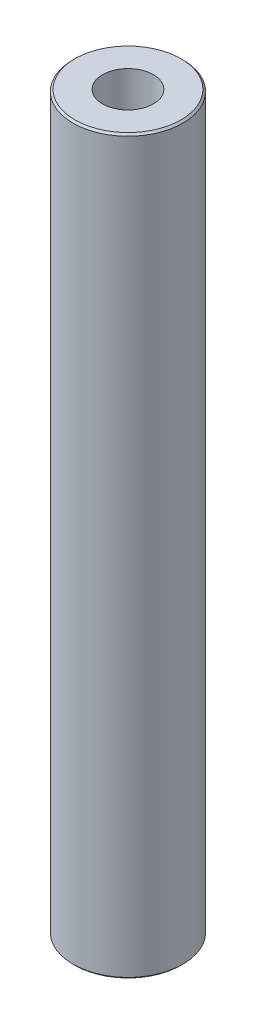
SolidWorks part; units mm, degrees
ref_plane "Front Plane" through (0, 0, 0) normal (0, 0, 1) x (1, 0, 0)
ref_plane "Top Plane" through (0, 0, 0) normal (0, 1, 0) x (1, 0, 0)
ref_plane "Right Plane" through (0, 0, 0) normal (1, 0, 0) x (0, 0, -1)
sketch "Sketch1" plane through (0, 0, 0) normal (0, 1, 0) x (1, 0, 0)
  circle A0 centre (0, 0) radius 45
  dimension "SHAFT_OD" = 90
extrude "Boss-Extrude1" add sketch "Sketch1" along normal blind 600
sketch "Sketch2" plane through (0, 0, 0) normal (0, 1, 0) x (1, 0, 0)
  circle A0 centre (0, 0) radius 20.8063
  dimension "BORE_D" = 41.6126
extrude "Cut-Extrude1" cut sketch "Sketch2" along normal through all
chamfer "Chamfer1" distance 1.5423 angle 45 2 edges at (0, 600, 45) (0, 0, 45)
